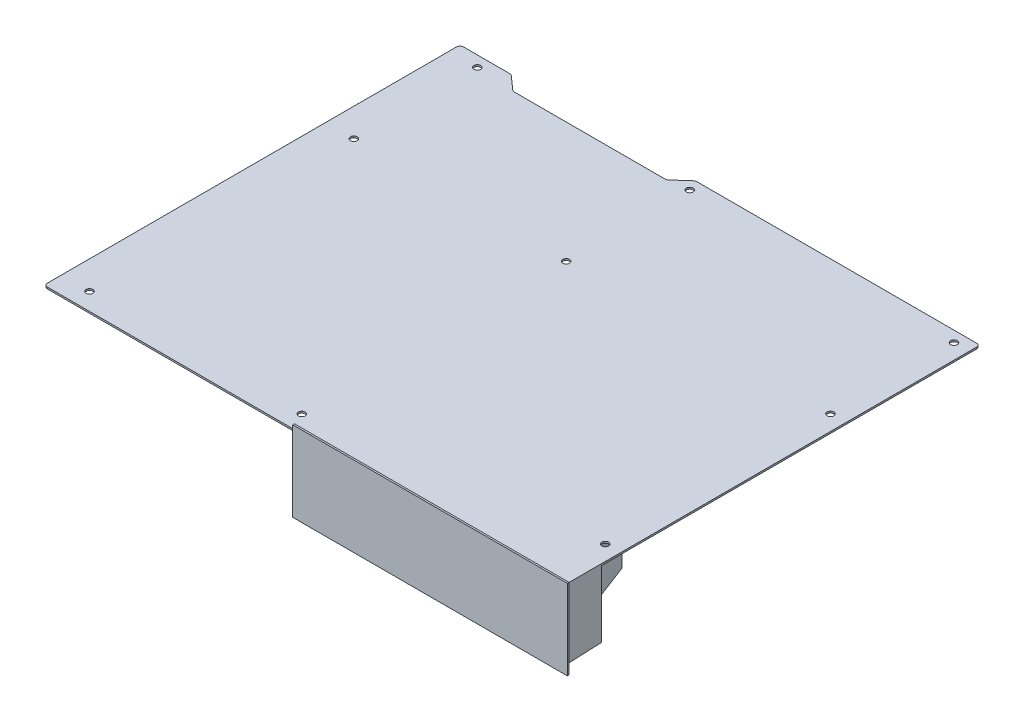
SolidWorks part; units mm, degrees
ref_plane "Front" through (0, 0, 0) normal (0, 0, 1) x (1, 0, 0)
ref_plane "Top" through (0, 0, 0) normal (0, 1, 0) x (1, 0, 0)
ref_plane "Right" through (0, 0, 0) normal (1, 0, 0) x (0, 0, -1)
sketch "Sketch1" plane through (0, 0, 0) normal (0, 1, 0) x (1, 0, 0)
  line L0 (-122.4, 121.92) -> (-122.4, 113.92) construction
  line L2 (-152.4, 121.92) -> (-152.4, -121.92)
  line L3 (-152.4, -121.92) -> (152.4, -121.92)
  line L4 (152.4, 121.92) -> (152.4, -121.92)
  line L7 (-122.4, 113.92) -> (-14.4, 113.92) construction
  line L8 (-14.4, 113.92) -> (-14.4, 121.92) construction
  line L9 (-152.4, 121.92) -> (-122.4, 121.92)
  line L10 (-14.4, 121.92) -> (152.4, 121.92)
  line L11 (-113.4, 113.92) -> (-23.4, 113.92)
  line L12 (-113.4, 113.92) -> (-122.4, 121.92)
  line L13 (-23.4, 113.92) -> (-14.4, 121.92)
  line L14 (-152.4, -111.76) -> (152.4, -111.76) construction
  line L15 (-152.4, 43.18) -> (152.4, 43.18) construction
  line L16 (-152.4, 115.57) -> (152.4, 115.57) construction
  line L17 (-135.89, -121.92) -> (-135.89, 121.92) construction
  line L18 (-11.43, -121.92) -> (-11.43, 115.57) construction
  line L19 (143.51, -121.92) -> (143.51, 121.92) construction
  circle A0 centre (-11.43, -111.76) radius 1.9812
  circle A1 centre (143.51, -88.9) radius 1.9812
  circle A2 centre (-135.89, 43.18) radius 1.9812
  circle A3 centre (-11.43, 115.57) radius 1.9812
  circle A4 centre (-135.89, 115.57) radius 1.9812
  circle A5 centre (143.51, 115.57) radius 1.9812
  circle A6 centre (-135.89, -111.76) radius 1.9812
  circle A7 centre (143.51, 43.18) radius 1.9812
  circle A8 centre (-11.43, 43.18) radius 1.9812
  point P0 (0, 0)
  point P12 (-68.4, 113.92)
  point P13 (-68.4, 113.92)
  dimension "D13" = 3.9624
  dimension "D1" = 304.8
  dimension "D2" = 243.84
  dimension "D3" = 30
  dimension "D4" = 108
  dimension "D5" = 90
  dimension "D6" = 8
  dimension "D7" = 227.33
  dimension "D8" = 10.16
  dimension "D9" = 154.94
  dimension "D10" = 124.46
  dimension "D11" = 279.4
  dimension "D12" = 16.51
  dimension "D14" = 22.86
extrude "Boss-Extrude1" add sketch "Sketch1" along normal blind 1
fillet "Fillet1" radius 2 4 edges at (-14.4, 0.5, -121.92) (-23.4, 0.5, -113.92) (-122.4, 0.5, -121.92) (-113.4, 0.5, -113.92)
fillet "Fillet2" radius 2 3 edges at (-152.4, 0.5, 121.92) (152.4, 0.5, -121.92) (-152.4, 0.5, -121.92)
sketch "Sketch2" plane through (0, 0, 0) normal (0, -1, 0) x (1, 0, 0)
  line L0 (152.4, 121.92) -> (152.4, -119.92) construction
  line L1 (-2.6, 121.92) -> (152.4, 121.92)
  line L2 (-2.6, 121.92) -> (-2.6, 99.92)
  line L4 (152.4, 121.92) -> (152.4, 99.92)
  line L5 (152.4, 99.92) -> (134.32, 91.3694)
  line L6 (134.32, 91.3694) -> (122.5293, 57.92)
  line L7 (-150.4, 121.92) -> (152.4, 121.92) construction
  line L8 (24.5293, 57.92) -> (122.5293, 57.92)
  line L9 (-2.6, 99.92) -> (24.5293, 57.92)
  point P0 (134.32, 91.3694)
  dimension "D1" = 155
  dimension "D2" = 22
  dimension "D3" = 98
  dimension "D4" = 50
  dimension "D5" = 20
  dimension "D6" = 64
extrude "Boss-Extrude2" add sketch "Sketch2" along normal blind 40
sketch "Sketch3" plane through (0, 0, 121.92) normal (0, 0, 1) x (1, 0, 0)
  line L0 (152.4, -40) -> (-2.6, -40) construction
  line L1 (155.4, -43) -> (-5.6, -43)
  line L2 (155.4, -43) -> (155.4, 4)
  line L3 (155.4, 4) -> (-5.6, 4)
  line L4 (-5.6, -43) -> (-5.6, 4)
  line L5 (-150.4, 1) -> (152.4, 1) construction
  line L6 (152.4, 1) -> (152.4, -40) construction
  line L7 (-2.6, -40) -> (-2.6, 0) construction
  dimension "D1" = 3
  dimension "D2" = 3
  dimension "D3" = 3
  dimension "D4" = 3
extrude "Boss-Extrude3" add sketch "Sketch3" along normal blind 1
sketch "Sketch4" plane through (0, 0, 0) normal (1, 0, 0) x (0, 0, -1)
  line L2 (-55.6754, -37) -> (-121.92, -40)
  line L5 (-55.6754, -37) -> (-55.6754, -43.769)
  line L6 (-55.6754, -43.769) -> (-121.92, -43.769)
  line L7 (-121.92, -43.769) -> (-121.92, -40)
extrude "Cut-Extrude1" cut sketch "Sketch4" along normal mid plane 450
